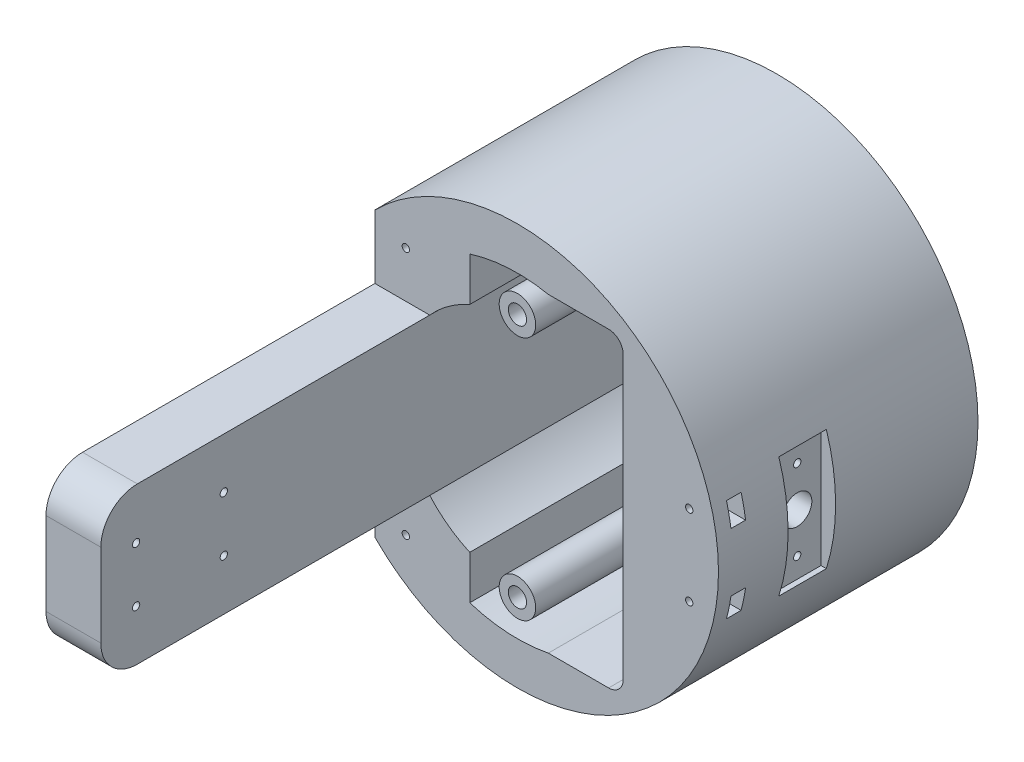
SolidWorks part; units mm, degrees
ref_plane "Front Plane" through (0, 0, 0) normal (0, 0, 1) x (1, 0, 0)
ref_plane "Top Plane" through (0, 0, 0) normal (0, 1, 0) x (1, 0, 0)
ref_plane "Right Plane" through (0, 0, 0) normal (1, 0, 0) x (0, 0, -1)
sketch "Sketch1" plane through (0, 0, 0) normal (0, 0, 1) x (1, 0, 0)
  line L0 (1.5, -40) -> (-1.5, -40)
  line L3 (1.5, 40) -> (-1.5, 40)
  circle A0 centre (0, 0) radius 55
  arc A2 (1.5, -40) -> (11.5, -30) centre (1.5, -30) ccw
  arc A3 (-11.5, -30) -> (-1.5, -40) centre (-1.5, -30) ccw
  arc A6 (11.5, 30) -> (1.5, 40) centre (1.5, 30) ccw
  arc A7 (-1.5, 40) -> (-11.5, 30) centre (-1.5, 30) ccw
  arc A9 (11.5, -30) -> (11.5, 30) centre (0, 0) ccw
  arc A10 (-11.5, 30) -> (-11.5, -30) centre (0, 0) ccw
  dimension "D1" = 110
extrude "Boss-Extrude1" add sketch "Sketch1" along normal blind 40
sketch "Sketch2" plane through (0, 0, 0) normal (0, 0, -1) x (-1, 0, 0)
  line L0 (-28.9387, 37.6605) -> (0, 0) construction
  line L5 (0, 0) -> (-28.9387, -42.5) construction
  line L6 (-8.4443, 37.1956) -> (-8.4443, 50.4631) construction
  line L7 (-28.9387, 42.5) -> (0, 0) construction
  line L8 (-8.4443, 42.5) -> (-28.9387, 42.5)
  line L9 (-8.4443, 42.5) -> (-8.4443, -42.5)
  line L10 (-8.4443, -42.5) -> (-28.9387, -42.5)
  line L11 (-28.9387, 42.5) -> (-28.9387, -42.5)
  arc A0 (-1.5, 40) -> (-11.5, 30) centre (-1.5, 30) ccw construction
  arc A1 (-1.5, 40) -> (-11.5, 30) centre (-1.5, 30) ccw construction
  point P13 (-8.4443, 37.1956)
  dimension "D1" = 20.4997
  dimension "D2" = 85
extrude "Cut-Extrude1" cut sketch "Sketch2" against normal through all
sketch "Sketch3" plane through (0, 0, 0) normal (0, 0, -1) x (-1, 0, 0)
  line L0 (-28.9387, 13.957) -> (-28.9387, -13.957)
  arc A0 (-28.9387, 13.957) -> (-28.9387, -13.957) centre (0, 0) ccw construction
  arc A1 (-28.9387, 13.957) -> (-28.9387, -13.957) centre (0, 0) ccw
extrude "Boss-Extrude2" add sketch "Sketch3" against normal through all
sketch "Sketch4" plane through (28.9387, 0, 0) normal (-1, 0, 0) x (0, 0, 1)
  line L1 (0, 42.5) -> (40, 42.5)
  line L2 (0, 42.5) -> (0, -42.5)
  line L3 (0, -42.5) -> (40, -42.5)
  line L4 (40, 42.5) -> (40, -42.5)
extrude "Cut-Extrude2" cut sketch "Sketch4" against normal blind 0.0053
fillet "Fillet1" radius 4 2 edges at (28.944, -42.5, 20) (28.944, 42.5, 20)
ref_plane "Plane1" through (55, 0, 0) normal (1, 0, 0) x (0, 0, -1)
sketch "Sketch5" plane through (55, 0, 0) normal (1, 0, 0) x (0, 0, -1)
  line L0 (-40, 55) -> (0, -55) construction
  line L1 (0, 55) -> (-40, -55) construction
  circle A0 centre (-18.4562, 0) radius 4
  point P13 (-20, 0)
  dimension "D1" = 8
  dimension "D2" = 1.5438
extrude "Cut-Extrude3" cut sketch "Sketch5" against normal up to surface (26.056 mm away) up to face at (28.944, 0, 20)
sketch "Sketch6" plane through (55, 0, 0) normal (1, 0, 0) x (0, 0, -1)
  line L1 (-11.9562, -16.5) -> (-24.9562, -16.5)
  line L2 (-11.9562, -16.5) -> (-11.9562, 16.5)
  line L3 (-11.9562, 16.5) -> (-24.9562, 16.5)
  line L4 (-24.9562, -16.5) -> (-24.9562, 16.5)
  line L5 (-11.9562, -16.5) -> (-24.9562, 16.5) construction
  line L6 (-11.9562, 16.5) -> (-24.9562, -16.5) construction
  point P0 (-18.4562, 0)
  dimension "D1" = 33
  dimension "D2" = 13
extrude "Cut-Extrude4" cut sketch "Sketch6" against normal blind 4
sketch "Sketch7" plane through (51, 0, 0) normal (1, 0, 0) x (0, 0, -1)
  circle A0 centre (-18.4562, 0) radius 4 construction
  circle A1 centre (-18.4562, 0) radius 4 construction
  circle A2 centre (-18.4562, 11) radius 1
  circle A3 centre (-18.4562, -11) radius 1
  dimension "D1" = 2
  dimension "D2" = 11
  dimension "D3" = 11
extrude "Cut-Extrude5" cut sketch "Sketch7" against normal up to surface (22.056 mm away) up to face at (28.944, 0, 22.4562)
ref_axis "Axis1" through (28.944, 11, 18.4562) along (1, 0, 0)
ref_axis "Axis2" through (28.944, -11, 18.4562) along (1, 0, 0)
sketch "Sketch8" plane through (0, 0, 0) normal (0, 0, -1) x (-1, 0, 0)
  line L0 (-47, -14) -> (-44.2967, -11) construction
  line L1 (-47, 14) -> (-43, 14)
  line L2 (-47, 14) -> (-47, 8)
  line L3 (-47, 8) -> (-43, 8)
  line L4 (-43, 14) -> (-43, 8)
  line L5 (-47, -8) -> (-43, -8)
  line L6 (-47, -8) -> (-47, -14)
  line L7 (-47, -14) -> (-43, -14)
  line L8 (-43, -8) -> (-43, -14)
  line L9 (-28.944, -11) -> (-51, -11) construction
  line L10 (-44.2967, -11) -> (-47, -8) construction
  line L11 (-47, 8) -> (-45.4504, 11) construction
  line L12 (-28.944, 11) -> (-51, 11) construction
  line L13 (-45.4504, 11) -> (-47, 14) construction
  line L14 (-55, 22) -> (-55, -22) construction
  dimension "D1" = 8
  dimension "D2" = 4
  dimension "D3" = 6
extrude "Cut-Extrude6" cut sketch "Sketch8" against normal through all
sketch "Sketch9" plane through (0, 0, 40) normal (0, 0, 1) x (1, 0, 0)
  line L0 (-24, 21.36) -> (-24, -21.36)
  arc A0 (-11.5, 30) -> (-11.5, -30) centre (0, 0) ccw construction
  arc A1 (-24, 21.36) -> (-24, -21.36) centre (0, 0) ccw
  dimension "D1" = 24
extrude "Boss-Extrude3" add sketch "Sketch9" against normal through all
sketch "Sketch10" plane through (0, 0, 40) normal (0, 0, 1) x (1, 0, 0)
  line L0 (-39, 38.7814) -> (-39, -38.7814)
  circle A0 centre (0, 0) radius 55 construction
  arc A1 (-39, 38.7814) -> (-39, -38.7814) centre (0, 0) ccw
  dimension "D1" = 39
extrude "Cut-Extrude7" cut sketch "Sketch10" against normal through all
sketch "Sketch11" plane through (0, 0, 40) normal (0, 0, 1) x (1, 0, 0)
  line L0 (-39, -38.7814) -> (-39, 38.7814) construction
  line L1 (-24, -21.36) -> (-24, 21.36) construction
  line L2 (-39, -21.36) -> (-39, 21.36)
  line L3 (-24, -21.36) -> (-24, 21.36)
  line L4 (-24, 21.36) -> (-39, 21.36)
  line L5 (-24, -21.36) -> (-39, -21.36)
extrude "Boss-Extrude4" add sketch "Sketch11" along normal blind 93.9795
sketch "Sketch12" plane through (-24, 0, 0) normal (1, 0, 0) x (0, 0, -1)
  circle A0 centre (-124.3295, -7.4744) radius 1
  circle A1 centre (-124.3295, 7.5256) radius 1
  circle A2 centre (-100.3295, -7.4744) radius 1
  circle A3 centre (-100.3295, 7.5256) radius 1
  point P12 (0, 0)
  point P13 (0, 0)
  point P14 (0, 0)
  point P15 (0, 0)
extrude "Cut-Extrude8" cut sketch "Sketch12" against normal through all
sketch "Sketch13" plane through (-39, 0, 0) normal (-1, 0, 0) x (0, 0, 1)
  circle A0 centre (100.3295, 7.5256) radius 2.45
  circle A1 centre (124.3295, 7.5256) radius 2.45
  circle A2 centre (124.3295, -7.4744) radius 2.45
  circle A3 centre (100.3295, -7.4744) radius 2.45
  dimension "D1" = 4.9
extrude "Cut-Extrude9" cut sketch "Sketch13" against normal blind 4
sketch "Sketch14" plane through (0, 0, 40) normal (0, 0, 1) x (1, 0, 0)
  line L0 (-24, -21.36) -> (-24, 21.36) construction
  line L1 (-24, -21.36) -> (-24, 21.36)
  line L2 (-13.0476, 29.36) -> (-13.0476, 41.3197)
  line L3 (-13.0476, -29.36) -> (-13.0476, -41.3197)
  line L4 (28.944, -32.2459) -> (28.944, 32.2459)
  line L5 (28.944, -38.5) -> (28.944, 38.5) construction
  arc A0 (28.944, 32.2459) -> (-13.0476, 41.3197) centre (0, 0) ccw
  arc A3 (-24, -21.36) -> (-13.0476, -29.36) centre (0, 0) ccw
  arc A4 (-13.0476, 29.36) -> (-24, 21.36) centre (0, 0) ccw
  arc A5 (-13.0476, -41.3197) -> (28.944, -32.2459) centre (0, 0) ccw
extrude "Cut-Extrude10" cut sketch "Sketch14" against normal through all
sketch "Sketch15" plane through (0, 0, 0) normal (0, 0, -1) x (-1, 0, 0)
  line L0 (39, 38.7814) -> (39, -38.7814)
  line L1 (-24.944, -42.5) -> (-8.4443, -42.5) construction
  line L2 (13.0476, -29.36) -> (13.0476, -41.3197) construction
  line L3 (24, -21.36) -> (24, 21.36) construction
  line L4 (13.0476, 41.3197) -> (13.0476, 29.36) construction
  line L5 (-28.944, 38.5) -> (-28.944, -38.5) construction
  line L6 (-8.4443, 42.5) -> (-24.944, 42.5) construction
  line L7 (-24.944, -42.5) -> (-8.4443, -42.5)
  line L8 (13.0476, -29.36) -> (13.0476, -41.3197)
  line L9 (24, -21.36) -> (24, 21.36)
  line L10 (13.0476, 41.3197) -> (13.0476, 29.36)
  line L11 (-28.944, 38.5) -> (-28.944, -38.5)
  line L12 (-8.4443, 42.5) -> (-24.944, 42.5)
  line L13 (-43, 14) -> (-47, 14) construction
  line L14 (-47, 14) -> (-47, 8) construction
  line L15 (-43, 8) -> (-43, 14) construction
  line L16 (-47, 8) -> (-43, 8) construction
  line L17 (-43, -8) -> (-47, -8) construction
  line L18 (-43, -14) -> (-43, -8) construction
  line L19 (-47, -8) -> (-47, -14) construction
  line L20 (-47, -14) -> (-43, -14) construction
  line L21 (-47, -14) -> (-43, -14)
  line L22 (-47, -8) -> (-47, -14)
  line L23 (-43, -14) -> (-43, -8)
  line L24 (-43, -8) -> (-47, -8)
  line L25 (-47, 8) -> (-43, 8)
  line L26 (-43, 8) -> (-43, 14)
  line L27 (-47, 14) -> (-47, 8)
  line L28 (-43, 14) -> (-47, 14)
  arc A0 (39, 38.7814) -> (39, -38.7814) centre (0, 0) ccw
  arc A1 (39, 38.7814) -> (39, -38.7814) centre (0, 0) ccw construction
  arc A2 (-28.944, -38.5) -> (-24.944, -42.5) centre (-24.944, -38.5) ccw construction
  arc A3 (-8.4443, -42.5) -> (13.0476, -41.3197) centre (0, 0) ccw construction
  arc A4 (13.0476, -29.36) -> (24, -21.36) centre (0, 0) ccw construction
  arc A5 (24, 21.36) -> (13.0476, 29.36) centre (0, 0) ccw construction
  arc A6 (13.0476, 41.3197) -> (-8.4443, 42.5) centre (0, 0) ccw construction
  arc A7 (-24.944, 42.5) -> (-28.944, 38.5) centre (-24.944, 38.5) ccw construction
  arc A8 (-28.944, -38.5) -> (-24.944, -42.5) centre (-24.944, -38.5) ccw
  arc A9 (-8.4443, -42.5) -> (13.0476, -41.3197) centre (0, 0) ccw
  arc A10 (13.0476, -29.36) -> (24, -21.36) centre (0, 0) ccw
  arc A11 (24, 21.36) -> (13.0476, 29.36) centre (0, 0) ccw
  arc A12 (13.0476, 41.3197) -> (-8.4443, 42.5) centre (0, 0) ccw
  arc A13 (-24.944, 42.5) -> (-28.944, 38.5) centre (-24.944, 38.5) ccw
extrude "Boss-Extrude5" add sketch "Sketch15" along normal blind 22
sketch "Sketch16" plane through (0, 0, -22) normal (0, 0, -1) x (-1, 0, 0)
  line L0 (39, -38.7814) -> (39, 38.7814) construction
  line L1 (39, -38.7814) -> (39, 38.7814)
  line L2 (-47, -14) -> (-43, -14) construction
  line L3 (-43, -14) -> (-43, -8) construction
  line L4 (-43, -8) -> (-47, -8) construction
  line L5 (-47, -8) -> (-47, -14) construction
  line L6 (-47, 8) -> (-43, 8) construction
  line L7 (-43, 8) -> (-43, 14) construction
  line L8 (-43, 14) -> (-47, 14) construction
  line L9 (-47, 14) -> (-47, 8) construction
  line L10 (-47, -14) -> (-43, -14)
  line L11 (-43, -14) -> (-43, -8)
  line L12 (-43, -8) -> (-47, -8)
  line L13 (-47, -8) -> (-47, -14)
  line L14 (-47, 8) -> (-43, 8)
  line L15 (-43, 8) -> (-43, 14)
  line L16 (-43, 14) -> (-47, 14)
  line L17 (-47, 14) -> (-47, 8)
  arc A0 (39, 38.7814) -> (39, -38.7814) centre (0, 0) ccw construction
  arc A1 (39, 38.7814) -> (39, -38.7814) centre (0, 0) ccw
extrude "Boss-Extrude6" add sketch "Sketch16" along normal blind 5
sketch "Sketch17" plane through (0, 0, -22) normal (0, 0, 1) x (1, 0, 0)
  circle A0 centre (0, 33.5) radius 5
  circle A1 centre (0, -33.5) radius 5
  point P6 (0, -33.5)
  dimension "D1" = 10
extrude "Boss-Extrude7" add sketch "Sketch17" along normal up to surface (62 mm away) up to face at (-2.3045, 0, 40)
sketch "Sketch18" plane through (0, 0, 40) normal (0, 0, 1) x (1, 0, 0)
  line L39 (-13.0476, 29.36) -> (-13.0476, 41.3197)
  line L40 (8.4443, 42.5) -> (24.944, 42.5)
  line L41 (28.944, 38.5) -> (28.944, -38.5)
  line L42 (24.944, -42.5) -> (8.4443, -42.5)
  line L43 (-13.0476, -41.3197) -> (-13.0476, -29.36)
  line L44 (-24, -21.36) -> (-39, -21.36)
  line L45 (-39, -21.36) -> (-39, -38.7814)
  line L46 (-39, 38.7814) -> (-39, 21.36)
  line L47 (-24, -21.36) -> (-39, -21.36)
  line L48 (-13.0476, 29.36) -> (-13.0476, 41.3197)
  line L49 (8.4443, 42.5) -> (24.944, 42.5)
  line L50 (28.944, 38.5) -> (28.944, -38.5)
  line L51 (24.944, -42.5) -> (8.4443, -42.5)
  line L52 (-13.0476, -41.3197) -> (-13.0476, -29.36)
  line L54 (-39, -21.36) -> (-39, -38.7814)
  line L55 (-39, 38.7814) -> (-39, 21.36)
  line L57 (-39, 21.36) -> (-24, 21.36)
  line L58 (-39, 21.36) -> (-24, 21.36)
  arc A23 (8.4443, 42.5) -> (-13.0476, 41.3197) centre (0, 0) ccw
  arc A24 (28.944, 38.5) -> (24.944, 42.5) centre (24.944, 38.5) ccw
  arc A25 (24.944, -42.5) -> (28.944, -38.5) centre (24.944, -38.5) ccw
  arc A26 (-13.0476, -41.3197) -> (8.4443, -42.5) centre (0, 0) ccw
  arc A27 (-39, -38.7814) -> (-39, 38.7814) centre (0, 0) ccw
  arc A28 (8.4443, 42.5) -> (-13.0476, 41.3197) centre (0, 0) ccw
  arc A29 (28.944, 38.5) -> (24.944, 42.5) centre (24.944, 38.5) ccw
  arc A30 (24.944, -42.5) -> (28.944, -38.5) centre (24.944, -38.5) ccw
  arc A31 (-13.0476, -41.3197) -> (8.4443, -42.5) centre (0, 0) ccw
  arc A32 (-39, -38.7814) -> (-39, 38.7814) centre (0, 0) ccw
  arc A35 (-24, -21.36) -> (-13.0476, -29.36) centre (0, 0) ccw
  arc A36 (-24, -21.36) -> (-13.0476, -29.36) centre (0, 0) ccw
  arc A37 (-13.0476, 29.36) -> (-24, 21.36) centre (0, 0) ccw
  arc A38 (-13.0476, 29.36) -> (-24, 21.36) centre (0, 0) ccw
  dimension "D1" = 0
extrude "Boss-Extrude8" add sketch "Sketch18" along normal blind 4
sketch "Sketch19" plane through (0, 0, 40) normal (0, 0, 1) x (1, 0, 0)
  circle A0 centre (0, 33.5) radius 5 construction
  circle A1 centre (0, -33.5) radius 5 construction
  circle A2 centre (0, 33.5) radius 5
  circle A3 centre (0, -33.5) radius 5
extrude "Boss-Extrude9" add sketch "Sketch19" along normal up to surface (4 mm away) up to face at (-2.3045, 0, 44)
sketch "Sketch20" plane through (0, 0, 44) normal (0, 0, 1) x (1, 0, 0)
  circle A0 centre (0, 33.5) radius 2.5
  circle A1 centre (0, -33.5) radius 2.5
  dimension "D1" = 5
extrude "Cut-Extrude11" cut sketch "Sketch20" against normal blind 7
sketch "Sketch21" plane through (0, 0, -22) normal (0, 0, 1) x (1, 0, 0)
  line L6 (8.4443, -42.5) -> (24.944, -42.5)
  line L7 (28.944, -38.5) -> (28.944, 38.5)
  line L8 (24.944, 42.5) -> (8.4443, 42.5)
  line L9 (-13.0476, 41.3197) -> (-13.0476, 29.36)
  line L10 (-24, 21.36) -> (-24, -21.36)
  line L11 (-13.0476, -29.36) -> (-13.0476, -41.3197)
  line L12 (8.4443, -42.5) -> (24.944, -42.5)
  line L13 (28.944, -38.5) -> (28.944, 38.5)
  line L14 (24.944, 42.5) -> (8.4443, 42.5)
  line L15 (-13.0476, 41.3197) -> (-13.0476, 29.36)
  line L16 (-24, 21.36) -> (-24, -21.36)
  line L17 (-13.0476, -29.36) -> (-13.0476, -41.3197)
  circle A0 centre (0, 33.5) radius 5 construction
  circle A1 centre (0, -33.5) radius 5 construction
  circle A2 centre (0, 33.5) radius 5
  circle A3 centre (0, -33.5) radius 5
  arc A6 (24.944, -42.5) -> (28.944, -38.5) centre (24.944, -38.5) ccw
  arc A7 (28.944, 38.5) -> (24.944, 42.5) centre (24.944, 38.5) ccw
  arc A8 (8.4443, 42.5) -> (-13.0476, 41.3197) centre (0, 0) ccw
  arc A9 (-13.0476, 29.36) -> (-24, 21.36) centre (0, 0) ccw
  arc A10 (-24, -21.36) -> (-13.0476, -29.36) centre (0, 0) ccw
  arc A11 (-13.0476, -41.3197) -> (8.4443, -42.5) centre (0, 0) ccw
  arc A12 (24.944, -42.5) -> (28.944, -38.5) centre (24.944, -38.5) ccw
  arc A13 (28.944, 38.5) -> (24.944, 42.5) centre (24.944, 38.5) ccw
  arc A14 (8.4443, 42.5) -> (-13.0476, 41.3197) centre (0, 0) ccw
  arc A15 (-13.0476, 29.36) -> (-24, 21.36) centre (0, 0) ccw
  arc A16 (-24, -21.36) -> (-13.0476, -29.36) centre (0, 0) ccw
  arc A17 (-13.0476, -41.3197) -> (8.4443, -42.5) centre (0, 0) ccw
  dimension "D1" = 0
extrude "Cut-Extrude12" cut sketch "Sketch21" against normal blind 1
sketch "Sketch22" plane through (0, 0, 44) normal (0, 0, 1) x (1, 0, 0)
  line L0 (47, 14) -> (47, 8) construction
  line L1 (47, -8) -> (47, -14) construction
  circle A0 centre (-30.5379, -34) radius 1
  circle A1 centre (-30.5379, 34) radius 1
  circle A2 centre (47, 11) radius 1
  circle A3 centre (47, -11) radius 1
extrude "Cut-Extrude13" cut sketch "Sketch22" against normal blind 10
ref_plane "Plane2" through (55, 0, 0) normal (1, 0, 0) x (0, 0, -1)
ref_axis "Axis3" through (47, 11, 34) along (0, 0, 1)
ref_axis "Axis4" through (47, -11, 34) along (0, 0, 1)
ref_axis "Axis5" through (-30.5379, -34, 34) along (0, 0, 1)
ref_axis "Axis6" through (-30.5379, 34, 34) along (0, 0, 1)
sketch "Sketch23" plane through (55, 0, 0) normal (1, 0, 0) x (0, 0, -1)
  line L0 (-44, 55) -> (-44, -55) construction
  line L1 (-40, -8) -> (-36, -8)
  line L2 (-40, -8) -> (-40, -14)
  line L3 (-40, -14) -> (-36, -14)
  line L4 (-36, -8) -> (-36, -14)
  line L5 (-40, 14) -> (-36, 14)
  line L6 (-40, 14) -> (-40, 8)
  line L7 (-40, 8) -> (-36, 8)
  line L8 (-36, 14) -> (-36, 8)
  line L9 (-40, 8) -> (-37.4742, 11) construction
  line L10 (-34, 11) -> (-44, 11) construction
  line L11 (-37.4742, 11) -> (-40, 14) construction
  line L12 (-40, -14) -> (-38.1078, -11) construction
  line L13 (-34, -11) -> (-44, -11) construction
  line L14 (-38.1078, -11) -> (-40, -8) construction
  dimension "D1" = 6
  dimension "D2" = 4
  dimension "D3" = 4
extrude "Cut-Extrude14" cut sketch "Sketch23" against normal up to next
sketch "Sketch24" plane through (-39, 0, 0) normal (-1, 0, 0) x (0, 0, 1)
  line L11 (44, 38.7814) -> (44, 21.36) construction
  line L12 (36.5, 37.5) -> (40.5, 37.5)
  line L13 (36.5, 37.5) -> (36.5, 30.5)
  line L14 (36.5, 30.5) -> (40.5, 30.5)
  line L15 (40.5, 37.5) -> (40.5, 30.5)
  line L16 (36.5, 37.5) -> (39.8933, 34) construction
  line L17 (34, 34) -> (44, 34) construction
  line L18 (39.8933, 34) -> (36.5, 30.5) construction
  line L19 (36.5, -37.1462) -> (38.8573, -34) construction
  line L20 (36.5, -30.8538) -> (40.5, -30.8538)
  line L21 (36.5, -30.8538) -> (36.5, -37.1462)
  line L22 (36.5, -37.1462) -> (40.5, -37.1462)
  line L23 (40.5, -30.8538) -> (40.5, -37.1462)
  line L24 (34, -34) -> (44, -34) construction
  line L25 (38.8573, -34) -> (36.5, -30.8538) construction
  dimension "D1" = 3.5
  dimension "D2" = 4
  dimension "D3" = 7
extrude "Cut-Extrude15" cut sketch "Sketch24" against normal blind 13
sketch "Sketch25" plane through (0, 0, -27) normal (0, 0, -1) x (-1, 0, 0)
  line L0 (8.8741, -40) -> (-8.8741, 40) construction
  line L1 (-8.8741, -40) -> (8.8741, 40) construction
  circle A0 centre (0, 0) radius 3.5
  dimension "D1" = 7
extrude "Cut-Extrude16" cut sketch "Sketch25" against normal up to next
sketch "Sketch26" plane through (0, 0, -27) normal (0, 0, -1) x (-1, 0, 0)
  circle A0 centre (0, 0) radius 3.5 construction
  circle A1 centre (0, 0) radius 3.5
  circle A2 centre (0, 0) radius 7.5
  dimension "D1" = 15
sketch "Sketch27" plane through (0, 0, -23) normal (0, 0, 1) x (1, 0, 0)
  circle A0 centre (0, 0) radius 3.5 construction
  circle A1 centre (0, 0) radius 3.5
  circle A2 centre (0, 0) radius 7.5
  dimension "D1" = 15
extrude "Boss-Extrude11" add sketch "Sketch27" along normal blind 9
fillet "Fillet3" radius 10 2 edges at (-31.5, -21.36, 133.9795) (-31.5, 21.36, 133.9795)
fillet "Fillet4" radius 8 2 edges at (5, 33.5, -23) (5, -33.5, -23)
fillet "Fillet5" radius 4 1 edges at (7.5, 0, -23)
